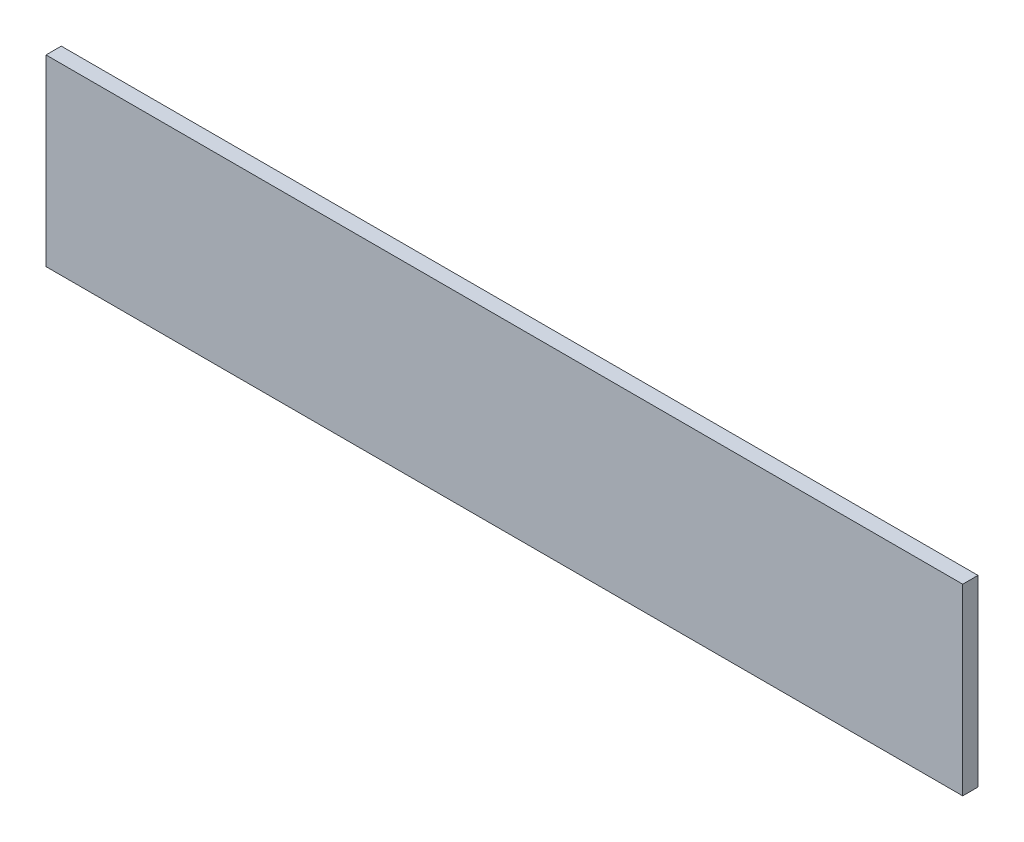
SolidWorks part; units mm, degrees
ref_plane "Plan de face" through (0, 0, 0) normal (0, 0, 1) x (1, 0, 0)
ref_plane "Plan de dessus" through (0, 0, 0) normal (0, 1, 0) x (1, 0, 0)
ref_plane "Plan de droite" through (0, 0, 0) normal (1, 0, 0) x (0, 0, -1)
sketch "Esquisse1" plane through (0, 0, 0) normal (0, 0, 1) x (1, 0, 0)
  line L1 (0, 0) -> (600, 0)
  line L2 (0, 0) -> (0, 120)
  line L3 (0, 120) -> (600, 120)
  line L4 (600, 0) -> (600, 120)
  dimension "D1" = 120
  dimension "D2" = 600
extrude "Boss.-Extru.1" add sketch "Esquisse1" along normal blind 10
